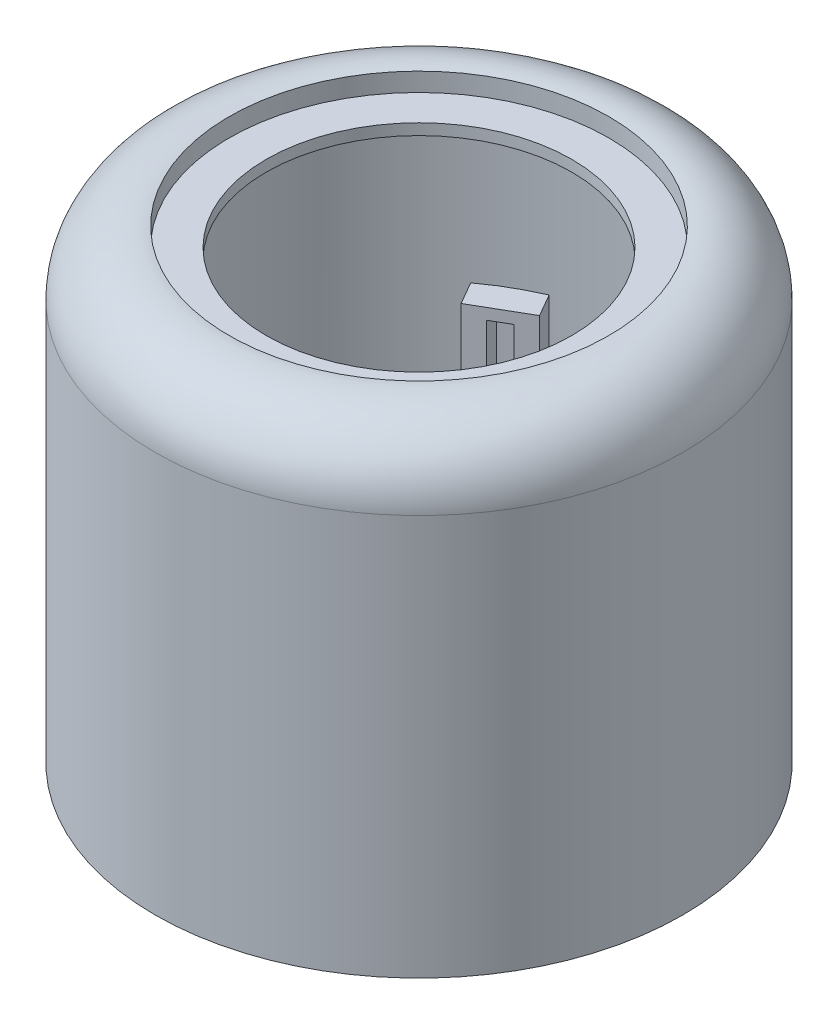
SolidWorks part; units mm, degrees
material "PE 低/中密度"
ref_plane "前视基准面" through (0, 0, 0) normal (0, 0, 1) x (1, 0, 0)
ref_plane "上视基准面" through (0, 0, 0) normal (0, 1, 0) x (1, 0, 0)
ref_plane "右视基准面" through (0, 0, 0) normal (1, 0, 0) x (0, 0, -1)
sketch "草图4" plane through (0, 0, 0) normal (1, 0, 0) x (0, 0, -1)
  line L0 (0, 0) -> (0, 46.8875) construction
  line L1 (16.5, 48.2) -> (16.5, 47)
  line L2 (16.5, 47) -> (22, 47)
  line L3 (27, 42) -> (27, 0)
  line L4 (27, 0) -> (28.5, 0)
  line L5 (28.5, 0) -> (28.5, 43.2718)
  line L7 (20.5, 50.2) -> (20.5, 48.2)
  line L8 (20.5, 48.2) -> (16.5, 48.2)
  arc A0 (28.5, 43.2718) -> (20.5, 50.2) centre (21.5, 43.2718) ccw
  arc A1 (22, 47) -> (27, 42) centre (22, 42) cw
  point P5 (20.5, 49.2)
  point P14 (28, 39.5)
  dimension "D9" = 7
  dimension "D10" = 5
  dimension "D1" = 16.5
  dimension "D2" = 1.2
  dimension "D3" = 2
  dimension "D4" = 20.5
  dimension "D5" = 1.5
  dimension "D6" = 27
  dimension "D7" = 47
revolve "旋转1" add sketch "草图4" angle 360 about L0
sketch "草图5" plane through (0, 0, 0) normal (0, -1, 0) x (1, 0, 0)
  line L0 (0, 0) -> (34.322, 0) construction
  line L1 (28, 3.1) -> (24, 3.1)
  line L2 (28, -1.1) -> (24, -1.1)
  line L3 (28, -1.1) -> (28, -3.1)
  line L4 (28, -3.1) -> (24, -3.1)
  line L5 (24, -1.1) -> (24, -3.1)
  line L6 (24, 1.1) -> (24, 3.1)
  line L7 (28, 1.1) -> (24, 1.1)
  line L8 (28, 1.1) -> (28, 3.1)
  line L9 (16.6847, -22.6987) -> (14.6847, -19.2346)
  line L10 (12.9526, -20.2346) -> (14.6847, -19.2346)
  line L11 (14.9526, -23.6987) -> (12.9526, -20.2346)
  line L12 (14.9526, -23.6987) -> (16.6847, -22.6987)
  line L13 (13.0474, -24.7987) -> (11.3153, -25.7987)
  line L14 (13.0474, -24.7987) -> (11.0474, -21.3346)
  line L15 (11.0474, -21.3346) -> (9.3153, -22.3346)
  line L16 (11.3153, -25.7987) -> (9.3153, -22.3346)
  line L17 (-11.3153, -25.7987) -> (-9.3153, -22.3346)
  line L18 (-11.0474, -21.3346) -> (-9.3153, -22.3346)
  line L19 (-13.0474, -24.7987) -> (-11.0474, -21.3346)
  line L20 (-13.0474, -24.7987) -> (-11.3153, -25.7987)
  line L21 (-14.9526, -23.6987) -> (-16.6847, -22.6987)
  line L22 (-14.9526, -23.6987) -> (-12.9526, -20.2346)
  line L23 (-12.9526, -20.2346) -> (-14.6847, -19.2346)
  line L24 (-16.6847, -22.6987) -> (-14.6847, -19.2346)
  line L25 (-28, -3.1) -> (-24, -3.1)
  line L26 (-24, -1.1) -> (-24, -3.1)
  line L27 (-28, -1.1) -> (-24, -1.1)
  line L28 (-28, -1.1) -> (-28, -3.1)
  line L29 (-28, 1.1) -> (-28, 3.1)
  line L30 (-28, 1.1) -> (-24, 1.1)
  line L31 (-24, 1.1) -> (-24, 3.1)
  line L32 (-28, 3.1) -> (-24, 3.1)
  line L33 (-16.6847, 22.6987) -> (-14.6847, 19.2346)
  line L34 (-12.9526, 20.2346) -> (-14.6847, 19.2346)
  line L35 (-14.9526, 23.6987) -> (-12.9526, 20.2346)
  line L36 (-14.9526, 23.6987) -> (-16.6847, 22.6987)
  line L37 (-13.0474, 24.7987) -> (-11.3153, 25.7987)
  line L38 (-13.0474, 24.7987) -> (-11.0474, 21.3346)
  line L39 (-11.0474, 21.3346) -> (-9.3153, 22.3346)
  line L40 (-11.3153, 25.7987) -> (-9.3153, 22.3346)
  line L41 (11.3153, 25.7987) -> (9.3153, 22.3346)
  line L42 (11.0474, 21.3346) -> (9.3153, 22.3346)
  line L43 (13.0474, 24.7987) -> (11.0474, 21.3346)
  line L44 (13.0474, 24.7987) -> (11.3153, 25.7987)
  line L45 (14.9526, 23.6987) -> (16.6847, 22.6987)
  line L46 (14.9526, 23.6987) -> (12.9526, 20.2346)
  line L47 (12.9526, 20.2346) -> (14.6847, 19.2346)
  line L48 (16.6847, 22.6987) -> (14.6847, 19.2346)
  point P12 (0, 0)
  dimension "D1" = 2.2
  dimension "D2" = 24
  dimension "D3" = 28
  dimension "D4" = 2
  dimension "D5" = 6
extrude "凸台-拉伸1" add sketch "草图5" against normal blind 26
sketch "草图6" plane through (0, 26, 0) normal (0, 1, 0) x (1, 0, 0)
  line L0 (9.3153, -22.3346) -> (11.0653, -25.3657)
  line L1 (24, -3.1) -> (27.5, -3.1)
  line L2 (24, -3.1) -> (24, 3.1)
  line L3 (24, 3.1) -> (27.5, 3.1)
  line L4 (27.5, -3.1) -> (27.5, 3.1)
  line L5 (9.3153, -22.3346) -> (14.6847, -19.2346)
  line L6 (14.6847, -19.2346) -> (16.4347, -22.2657)
  line L7 (11.0653, -25.3657) -> (16.4347, -22.2657)
  line L8 (-14.6847, -19.2346) -> (-16.4347, -22.2657)
  line L9 (-14.6847, -19.2346) -> (-9.3153, -22.3346)
  line L10 (-9.3153, -22.3346) -> (-11.0653, -25.3657)
  line L11 (-16.4347, -22.2657) -> (-11.0653, -25.3657)
  line L12 (-24, 3.1) -> (-27.5, 3.1)
  line L13 (-24, 3.1) -> (-24, -3.1)
  line L14 (-24, -3.1) -> (-27.5, -3.1)
  line L15 (-27.5, 3.1) -> (-27.5, -3.1)
  line L16 (-9.3153, 22.3346) -> (-11.0653, 25.3657)
  line L17 (-9.3153, 22.3346) -> (-14.6847, 19.2346)
  line L18 (-14.6847, 19.2346) -> (-16.4347, 22.2657)
  line L19 (-11.0653, 25.3657) -> (-16.4347, 22.2657)
  line L20 (14.6847, 19.2346) -> (16.4347, 22.2657)
  line L21 (14.6847, 19.2346) -> (9.3153, 22.3346)
  line L22 (9.3153, 22.3346) -> (11.0653, 25.3657)
  line L23 (16.4347, 22.2657) -> (11.0653, 25.3657)
  dimension "D1" = 3.5
  dimension "D2" = 6
extrude "凸台-拉伸2" add sketch "草图6" against normal blind 1.2
sketch "草图7" plane through (0, 0, 0) normal (0, 0, 1) x (1, 0, 0)
  line L0 (-28.5, 0) -> (28.5, 0) construction
  circle A0 centre (0, 14.2) radius 1.4
  dimension "D1" = 2.8
  dimension "D2" = 14.2
extrude "切除-拉伸1" cut sketch "草图7" against normal up to next
